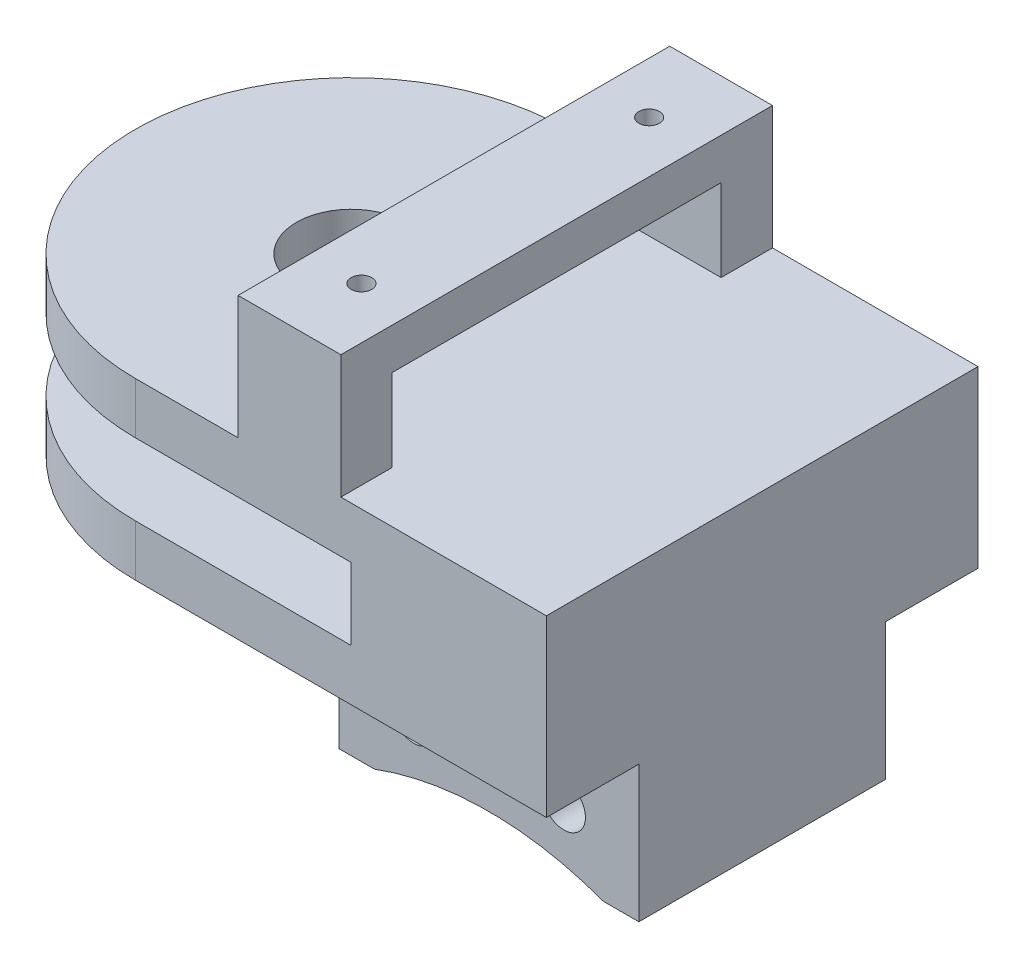
SolidWorks part; units mm, degrees
ref_plane "Front Plane" through (0, 0, 0) normal (0, 0, 1) x (1, 0, 0)
ref_plane "Top Plane" through (0, 0, 0) normal (0, 1, 0) x (1, 0, 0)
ref_plane "Right Plane" through (0, 0, 0) normal (1, 0, 0) x (0, 0, -1)
sketch "Sketch1" plane through (0, 0, 0) normal (0, 1, 0) x (1, 0, 0)
  line L0 (0, -13.335) -> (25.4, -13.335)
  line L1 (0, 13.335) -> (25.4, 13.335)
  line L2 (25.4, 13.335) -> (25.4, -13.335)
  circle A0 centre (0, 0) radius 12.7 construction
  circle A1 centre (0, 0) radius 13.335 construction
  circle A2 centre (0, 0) radius 3.3782
  arc A3 (11.5484, 6.6675) -> (11.5484, -6.6675) centre (0, 0) ccw construction
  arc A4 (0, 13.335) -> (0, -13.335) centre (0, 0) ccw
  dimension "D1" = 25.4
  dimension "D2" = 0.635
  dimension "D4" = 6.7564
  dimension "D3" = 25.4
extrude "Boss-Extrude1" add sketch "Sketch1" along normal blind 3.175 contours A3 A2 region at (7.6257, 0, 0)
sketch "Sketch2" plane through (0, 0, 0) normal (0, -1, 0) x (-1, 0, 0)
  line L3 (-25.4, 13.335) -> (-25.4, -13.335)
  line L5 (-13.335, 0) -> (-13.335, 13.335)
  line L6 (-25.4, 13.335) -> (-13.335, 13.335)
  line L7 (-13.335, 0) -> (-13.335, -13.335)
  line L8 (0, -13.335) -> (-25.4, -13.335) construction
  line L9 (-13.335, -13.335) -> (-25.4, -13.335)
  arc A3 (0, 13.335) -> (0, -13.335) centre (0, 0) ccw construction
extrude "Boss-Extrude2" add sketch "Sketch2" along normal blind 4.445 contours L3 L9 L7 L5 L6
ref_plane "Plane2" through (0, -2.2225, 0) normal (0, -1, 0) x (-1, 0, 0)
mirror "Mirror2" about plane through (0, -2.2225, 0) normal (0, -1, 0) of "Boss-Extrude1"
sketch "Sketch7" plane through (0, -7.62, 0) normal (0, -1, 0) x (-1, 0, 0)
  line L0 (-25.4, 13.335) -> (-25.4, 7.62) construction
  line L1 (-25.4, 13.335) -> (-25.4, -13.335) construction
  line L2 (0, 0) -> (-25.4, 0) construction
  line L3 (-25.4, -13.335) -> (-25.4, -7.62) construction
  line L5 (-25.4, 7.62) -> (-6.858, 7.62)
  line L6 (-25.4, 7.62) -> (-25.4, -7.62)
  line L7 (-25.4, -7.62) -> (-6.858, -7.62)
  line L8 (-6.858, 7.62) -> (-6.858, -7.62)
  dimension "D1" = 5.715
  dimension "D2" = 18.542
extrude "Boss-Extrude4" add sketch "Sketch7" along normal blind 8.4391
sketch "Sketch8" plane through (0, 0, -7.62) normal (0, 0, -1) x (-1, 0, 0)
  line L0 (-16.129, -7.62) -> (-16.129, -16.0591) construction
  line L1 (-16.129, -16.0591) -> (-25.4, -16.0591) construction
  line L2 (-20.7645, -16.0591) -> (-20.7645, -7.62) construction
  line L3 (-6.858, -7.62) -> (-25.4, -7.62) construction
  line L4 (-6.858, -16.0591) -> (-25.4, -16.0591) construction
  line L5 (0, -7.62) -> (-25.4, -7.62) construction
  circle A0 centre (-20.7645, -12.1285) radius 1.3335
  circle A1 centre (-11.4935, -12.1285) radius 1.3335
  dimension "D1" = 2.667
  dimension "D2" = 4.5085
extrude "Cut-Extrude3" cut sketch "Sketch8" against normal through all
sketch "Sketch9" plane through (0, 0, -7.62) normal (0, 0, -1) x (-1, 0, 0)
  line L0 (-16.129, -16.0591) -> (-16.129, -35.1091) construction
  line L1 (-6.858, -16.0591) -> (-25.4, -16.0591) construction
  line L2 (-16.129, -16.0591) -> (-16.129, -14.7891) construction
  circle A0 centre (-16.129, -35.1091) radius 20.32
  dimension "D1" = 1.27
  dimension "D2" = 19.05
extrude "Cut-Extrude4" cut sketch "Sketch9" against normal through all
sketch "Sketch11" plane through (0, 3.175, 0) normal (0, 1, 0) x (1, 0, 0)
  line L0 (0, 0) -> (25.4, 0) construction
  line L5 (6.35, -13.335) -> (6.35, 13.335) construction
  line L6 (0, -13.335) -> (25.4, -13.335) construction
  line L7 (25.4, 13.335) -> (25.4, -13.335) construction
  line L12 (0, 13.335) -> (25.4, 13.335) construction
  line L14 (6.35, 10.16) -> (12.7, 10.16)
  line L15 (6.35, -13.335) -> (12.7, -13.335) construction
  line L16 (6.35, -13.335) -> (6.35, 13.335) construction
  line L21 (6.35, 13.335) -> (12.7, 13.335) construction
  line L22 (12.7, -13.335) -> (12.7, 13.335) construction
  line L23 (6.35, -13.335) -> (12.7, -13.335)
  line L24 (6.35, -13.335) -> (6.35, -10.16)
  line L25 (6.35, -10.16) -> (12.7, -10.16)
  line L26 (12.7, -13.335) -> (12.7, -10.16)
  line L27 (12.7, 13.335) -> (12.7, 10.16)
  line L28 (6.35, 13.335) -> (12.7, 13.335)
  line L29 (6.35, 13.335) -> (6.35, 10.16)
  dimension "D1" = 6.35
  dimension "D2" = 6.35
  dimension "D3" = 3.175
extrude "Boss-Extrude8" add sketch "Sketch11" along normal blind 5.08 contours L24 L23 L26 L25 | L14 L27 L28 L29
sketch "Sketch14" plane through (0, 8.255, 0) normal (0, 1, 0) x (1, 0, 0)
  line L0 (9.525, 13.335) -> (9.525, -13.335) construction
  line L1 (12.7, -13.335) -> (6.35, -13.335)
  line L2 (12.7, -13.335) -> (12.7, 13.335)
  line L3 (12.7, 13.335) -> (6.35, 13.335)
  line L4 (6.35, -13.335) -> (6.35, 13.335)
  line L5 (0, 0) -> (25.4, 0) construction
  line L6 (25.4, 13.335) -> (25.4, -13.335) construction
  circle A0 centre (9.525, 8.89) radius 0.635
  circle A1 centre (9.525, -8.89) radius 0.635
  dimension "D1" = 1.27
  dimension "D2" = 4.445
extrude "Boss-Extrude9" add sketch "Sketch14" along normal blind 2.54
